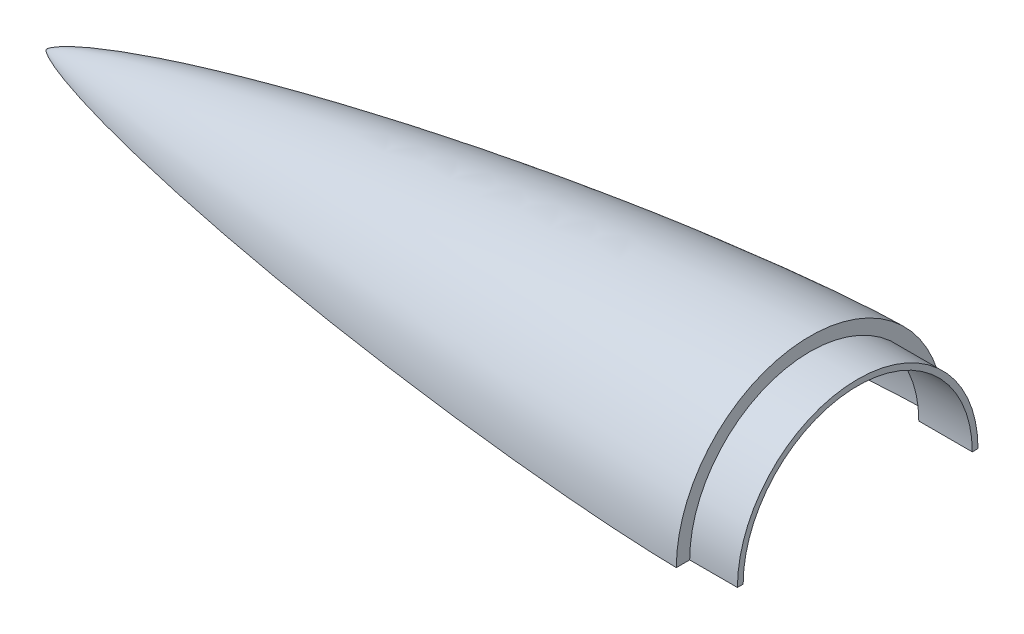
SolidWorks part; units mm, degrees
other "Markup1"
sketch "Sketch7" plane through (25, 20.25, 20.25) normal (0.5143, 0.3371, 0.7886) x (0.8495, -0.0739, -0.5224)
ref_plane "Front Plane" through (0, 0, 0) normal (0, 0, 1) x (1, 0, 0)
ref_plane "Top Plane" through (0, 0, 0) normal (0, 1, 0) x (1, 0, 0)
ref_plane "Right Plane" through (0, 0, 0) normal (1, 0, 0) x (0, 0, -1)
sketch "Sketch4" plane through (0, 0, 0) normal (1, 0, 0) x (0, 0, -1)
  circle A0 centre (0, 0) radius 60
  circle A1 centre (0, 0) radius 63
  dimension "D1" = 126
  dimension "D2" = 120
extrude "Boss-Extrude2" add sketch "Sketch4" along normal blind 25
sketch "Sketch6" plane through (0, 0, 0) normal (0, 0, 1) x (1, 0, 0)
  line L0 (-130.2728, 0) -> (79.642, 0) construction
  line L2 (0, 63) -> (0, -63) construction
  line L4 (0, 70) -> (0, 0)
  line L5 (0, 0) -> (-400, 0)
  spline S0 degree 4 poles (-400, 0) (-399.998, 0.0093) (-399.9928, 0.0274) (-399.9773, 0.062) (-399.9396, 0.1276) (-399.8836, 0.2062) (-399.809, 0.2968) (-399.7025, 0.413) (-399.5516, 0.5624) (-399.3075, 0.7801) (-398.8876, 1.1137) (-398.1712, 1.618) (-396.9075, 2.4008) (-394.6522, 3.6207) (-390.7239, 5.4641) (-384.1034, 8.16) (-372.6096, 12.2241) (-355.9796, 17.2897) (-334.9349, 22.9127) (-310.6252, 28.7002) (-285.5459, 34.1174) (-260.3776, 39.1035) (-235.1385, 43.7165) (-209.84, 47.9907) (-184.4899, 51.947) (-159.0936, 55.595) (-133.6551, 58.9354) (-108.1769, 61.9593) (-82.6608, 64.6462) (-60.302, 66.6695) (-41.1143, 68.1272) (-25.9755, 69.0596) (-16.0647, 69.5497) (-8.1849, 69.8428) (-3.5083, 69.9583) (-1.1695, 69.9952) (0, 70) knots 0 0 0 0 0 0.000093 0.000185 0.00037 0.000741 0.001038 0.001335 0.001914 0.002822 0.004242 0.006589 0.010497 0.017384 0.029361 0.049101 0.080536 0.136842 0.199711 0.262581 0.325451 0.38832 0.45119 0.51406 0.576929 0.639799 0.702668 0.765538 0.828408 0.891277 0.922712 0.954147 0.977074 0.988537 1 1 1 1 1 construction
  spline S1 degree 4 poles (-400, 0) (-399.998, 0.0093) (-399.9928, 0.0274) (-399.9773, 0.062) (-399.9396, 0.1276) (-399.8836, 0.2062) (-399.809, 0.2968) (-399.7025, 0.413) (-399.5516, 0.5624) (-399.3075, 0.7801) (-398.8876, 1.1137) (-398.1712, 1.618) (-396.9075, 2.4008) (-394.6522, 3.6207) (-390.7239, 5.4641) (-384.1034, 8.16) (-372.6096, 12.2241) (-355.9796, 17.2897) (-334.9349, 22.9127) (-310.6252, 28.7002) (-285.5459, 34.1174) (-260.3776, 39.1035) (-235.1385, 43.7165) (-209.84, 47.9907) (-184.4899, 51.947) (-159.0936, 55.595) (-133.6551, 58.9354) (-108.1769, 61.9593) (-82.6608, 64.6462) (-60.302, 66.6695) (-41.1143, 68.1272) (-25.9755, 69.0596) (-16.0647, 69.5497) (-8.1849, 69.8428) (-3.5083, 69.9583) (-1.1695, 69.9952) (0, 70) knots 0 0 0 0 0 0.000093 0.000185 0.00037 0.000741 0.001038 0.001335 0.001914 0.002822 0.004242 0.006589 0.010497 0.017384 0.029361 0.049101 0.080536 0.136842 0.199711 0.262581 0.325451 0.38832 0.45119 0.51406 0.576929 0.639799 0.702668 0.765538 0.828408 0.891277 0.922712 0.954147 0.977074 0.988537 1 1 1 1 1
  dimension "D1" = 140
revolve "Revolve1" add sketch "Sketch6" angle 360 about L0
shell "Shell1" thickness 3 removed face at (0, 0, -60)
sketch "Sketch8" plane through (0, 0, 0) normal (0, 1, 0) x (1, 0, 0)
  line L1 (-441.5009, 181.773) -> (70.4219, 181.773)
  line L2 (-441.5009, 181.773) -> (-441.5009, -205.6967)
  line L3 (-441.5009, -205.6967) -> (70.4219, -205.6967)
  line L4 (70.4219, 181.773) -> (70.4219, -205.6967)
extrude "Cut-Extrude1" cut sketch "Sketch8" against normal through all
